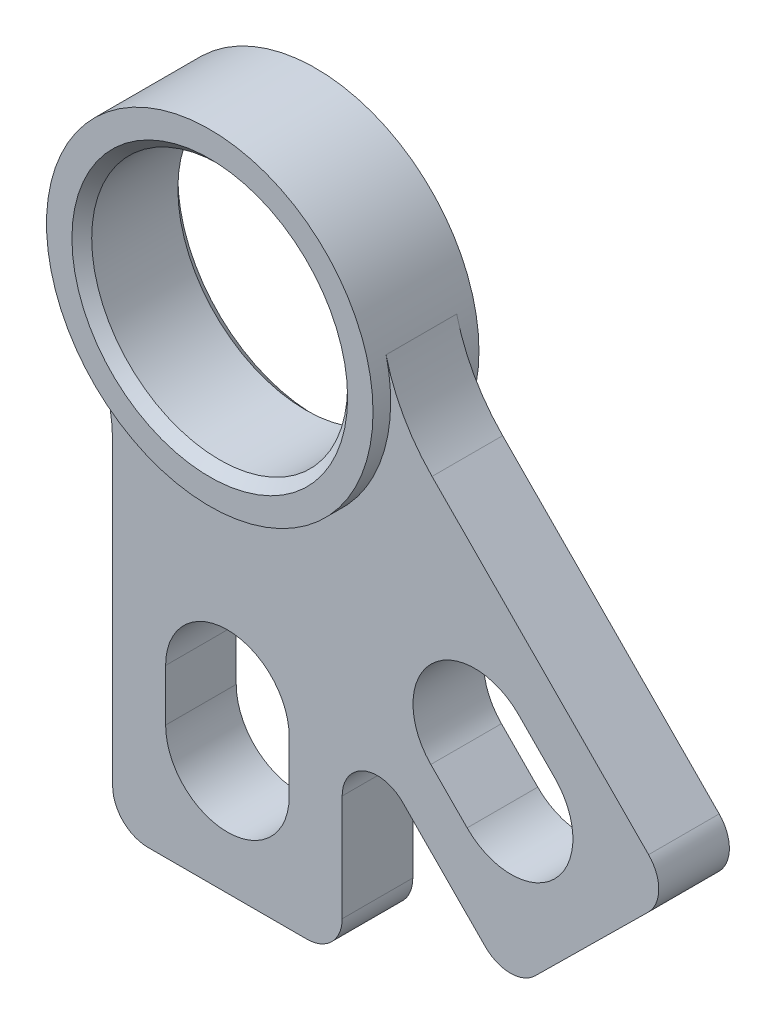
SolidWorks part; units mm, degrees
material "AISI 4130 Steel, annealed at 865C"
ref_plane "X-Y Datum" through (0, 0, 0) normal (0, 0, 1) x (1, 0, 0)
ref_plane "X-Z Datum" through (0, 0, 0) normal (0, 1, 0) x (1, 0, 0)
ref_plane "Y-Z Datum" through (0, 0, 0) normal (1, 0, 0) x (0, 0, -1)
sketch "Sketch1" plane through (0, 0, 0) normal (0, 0, 1) x (1, 0, 0)
  line L0 (0, -35.2861) -> (0, -30.6387) construction
  line L1 (-5.5562, -35.2861) -> (-5.5562, -30.6387)
  line L2 (5.5562, -35.2861) -> (5.5562, -30.6387)
  line L3 (25.5084, -25.8295) -> (22.2428, -22.5229) construction
  line L4 (21.555, -29.7337) -> (18.2895, -26.4271)
  line L5 (29.4617, -21.9253) -> (26.1962, -18.6187)
  line L6 (-10.3187, -15.7343) -> (-10.3187, -45.6048)
  line L7 (-10.3187, -45.6048) -> (10.3187, -45.6048)
  line L10 (25.4171, -40.4222) -> (40.101, -25.9208)
  line L11 (40.101, -25.9208) -> (18.398, -3.9446)
  line L14 (0, -40.8423) -> (0, -45.6048) construction
  line L15 (29.4126, -29.7829) -> (32.759, -33.1715) construction
  line L16 (27.829, -20.272) -> (31.2176, -16.9255) construction
  line L17 (-5.5562, -32.9624) -> (-10.3187, -32.9624) construction
  line L18 (-10.3187, -20.32) -> (10.3187, -20.32) construction
  line L19 (10.3187, -20.32) -> (10.3187, -45.6048) construction
  line L20 (5.5562, -32.9624) -> (10.3187, -32.9624) construction
  line L21 (0, -25.0825) -> (0, -20.32) construction
  line L22 (25.4171, -40.4222) -> (7.6502, -22.4316) construction
  line L23 (7.6502, -22.4316) -> (22.3341, -7.9302) construction
  line L24 (19.9222, -28.0804) -> (16.5336, -31.4269) construction
  line L25 (18.3386, -18.5695) -> (14.9922, -15.1809) construction
  line L29 (25.4171, -40.4222) -> (10.3187, -25.1337)
  line L30 (214.8127, -217.5173) -> (0, 0) construction
  line L31 (10.3187, -45.6048) -> (10.3187, -25.1337)
  line L35 (0, -295.7059) -> (0, 0) construction
  circle A0 centre (0, 0) radius 11.5062
  arc A1 (-5.5562, -35.2861) -> (5.5562, -35.2861) centre (0, -35.2861) ccw
  arc A2 (5.5562, -30.6387) -> (-5.5562, -30.6387) centre (0, -30.6387) ccw
  arc A3 (21.555, -29.7337) -> (29.4617, -21.9253) centre (25.5084, -25.8295) ccw
  arc A4 (26.1962, -18.6187) -> (18.2895, -26.4271) centre (22.2428, -22.5229) ccw
  arc A5 (14.2666, 3.4643) -> (-12.5852, -7.5598) centre (0, 0) ccw
  arc A6 (18.398, -3.9446) -> (14.2666, 3.4643) centre (29.6933, 7.2103) cw
  arc A7 (-10.3187, -15.7343) -> (-12.5852, -7.5598) centre (-26.1937, -15.7343) ccw
  arc A14 (-12.5852, -7.5598) -> (14.2666, 3.4643) centre (0, 0) ccw
  point P5 (0, -32.9624)
  point P11 (23.8756, -24.1762)
  point P24 (32.759, -33.1715)
  point P39 (29.4126, -29.7829)
  dimension "D1" = 23.0124
  dimension "D2" = 3.175
  dimension "D8" = 15.875
  dimension "D6" = 21.336
  dimension "D7" = 20.32
  dimension "D3" = 20.6375
  dimension "D4" = 4.7625
  dimension "D5" = 25.2848
extrude "Boss-Extrude2" add sketch "Sketch1" along normal mid plane 9.525 contours A5 A14 A0 region at (-5.4181, 13.197, 0)
extrude "Boss-Extrude3" add sketch "Sketch1<4>" along normal mid plane 6.35 contours A14 A7 L6 L7 L10 L11 A6 A4 L5 A3 L4 A2 L2 A1 L1 region at (10.5248, -24.813, 0)
sketch "Sketch1<4>" plane through (0, 0, 0) normal (0, 0, 1) x (1, 0, 0) same geometry as "Sketch1"
fillet "Fillet1" radius 3.175 5 edges at (-10.3187, -45.6048, 0) (40.101, -25.9208, 0) (10.3187, -25.1337, 0) (25.4171, -40.4222, 0) (10.3187, -45.6048, 0)
chamfer "Chamfer1" distance 0.889 angle 45 2 edges at (11.5062, 0, -4.7625) (11.5062, 0, 4.7625)
